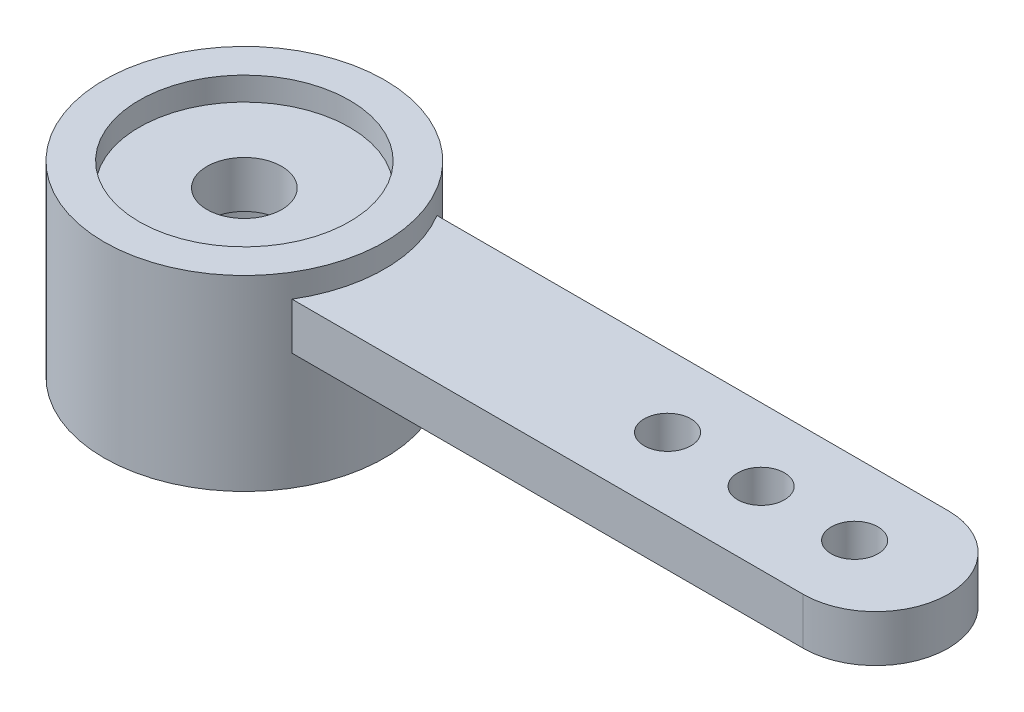
SolidWorks part; units mm, degrees
ref_plane "前视基准面" through (0, 0, 0) normal (0, 0, 1) x (1, 0, 0)
ref_plane "上视基准面" through (0, 0, 0) normal (0, 1, 0) x (1, 0, 0)
ref_plane "右视基准面" through (0, 0, 0) normal (1, 0, 0) x (0, 0, -1)
sketch "草图1" plane through (0, 0, 0) normal (0, 1, 0) x (1, 0, 0)
  line L0 (3, 0) -> (13.5, 0) construction
  line L1 (13.5, 1.575) -> (13.5, -1.575) construction
  line L2 (13.5, 1.5494) -> (2.5689, 1.5494)
  line L3 (13.5, -1.5494) -> (2.5689, -1.5494)
  line L4 (15.0494, 0) -> (13.0494, 0) construction
  circle A0 centre (0, 0) radius 3
  circle A1 centre (0, 0) radius 0.8
  arc A2 (13.5, -1.5494) -> (13.5, 1.5494) centre (13.5, 0) ccw
  circle A3 centre (0, 0) radius 2.25
  circle A4 centre (13.0494, 0) radius 0.5
  circle A5 centre (11.0494, 0) radius 0.5
  circle A6 centre (9.0494, 0) radius 0.5
  point P8 (13.5, 0)
  dimension "D1" = 6
  dimension "D2" = 1.6
  dimension "D5" = 4.5
  dimension "D7" = 1
  dimension "D3" = 10.5
  dimension "D4" = 3.15
  dimension "D6" = 2
  dimension "D8" = 3
extrude "凸台-拉伸1" add sketch "草图1" along normal blind 0.5 contours A0 A3 region at (2.8085, 0, -0.7814)
extrude "凸台-拉伸2" add sketch "草图1<7>" against normal blind 3.5 contours A0 A3 region at (2.8085, 0, -0.7814)
sketch "草图1<7>" plane through (0, 0, 0) normal (0, 1, 0) x (1, 0, 0) same geometry as "草图1"
extrude "凸台-拉伸3" add sketch "草图1<8>" against normal blind 1 contours A3 A1 | L3 A2 L2 A0 A6 A5 A4 region at (14.9208, 0, 0) region at (-2.1864, 0, 0)
sketch "草图1<8>" plane through (0, 0, 0) normal (0, 1, 0) x (1, 0, 0) same geometry as "草图1"
